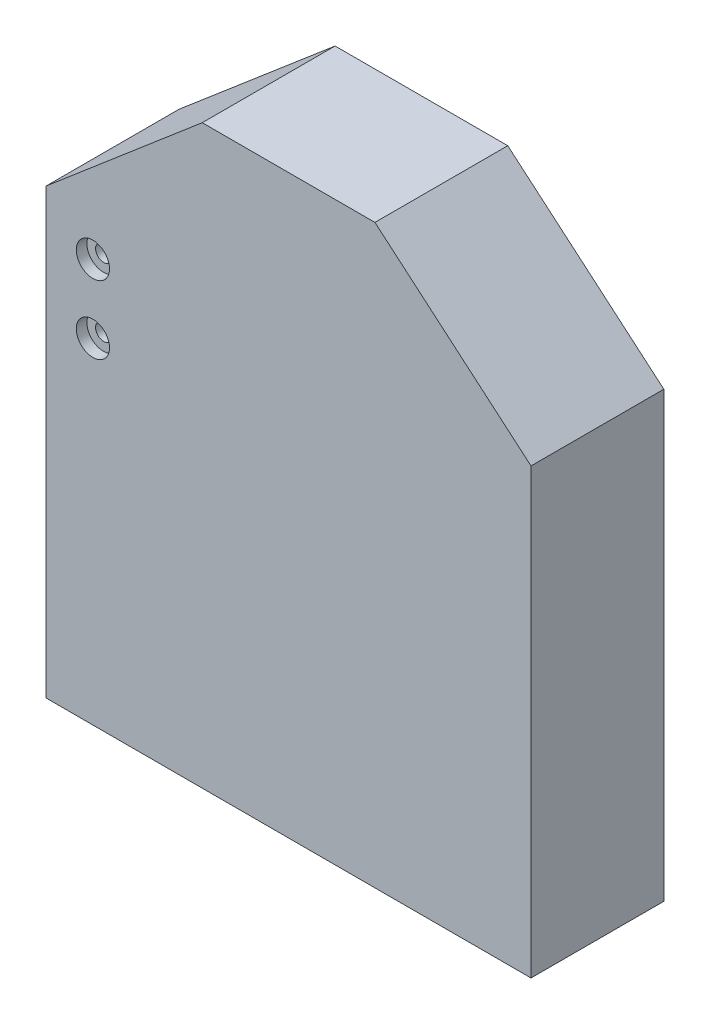
SolidWorks part; units mm, degrees
ref_plane "Front Plane" through (0, 0, 0) normal (0, 0, 1) x (1, 0, 0)
ref_plane "Top Plane" through (0, 0, 0) normal (0, 1, 0) x (1, 0, 0)
ref_plane "Right Plane" through (0, 0, 0) normal (1, 0, 0) x (0, 0, -1)
sketch "Base" plane through (0, 0, 0) normal (0, 0, 1) x (1, 0, 0)
  line L0 (-36.5, 30.8846) -> (-13, 50.8846)
  line L1 (-32.5, -27.5) -> (32.5, -27.5)
  line L2 (-32.5, -27.5) -> (-32.5, 27.5)
  line L3 (-32.5, 27.5) -> (32.5, 27.5)
  line L4 (32.5, -27.5) -> (32.5, 27.5)
  line L5 (-32.5, -27.5) -> (32.5, 27.5) construction
  line L6 (-32.5, 27.5) -> (32.5, -27.5) construction
  line L8 (-36.5, -30.8846) -> (-36.5, 30.8846)
  line L10 (36.5, -30.8846) -> (36.5, 30.8846)
  line L11 (-36.5, -30.8846) -> (36.5, 30.8846) construction
  line L12 (-36.5, 30.8846) -> (36.5, -30.8846) construction
  line L20 (13, 50.8846) -> (36.5, 30.8846)
  line L21 (-36.5, -30.8846) -> (36.5, -30.8846)
  line L22 (-21, -27.5) -> (-21, 5.6)
  line L23 (-21, 5.6) -> (-11, 5.6)
  line L24 (-11, 5.6) -> (-11, -27.5)
  line L25 (-11, -27.5) -> (-21, -27.5)
  line L26 (11, -27.5) -> (11, 5.6)
  line L27 (11, 5.6) -> (21, 5.6)
  line L28 (21, 5.6) -> (21, -27.5)
  line L29 (21, -27.5) -> (11, -27.5)
  line L30 (-21, 3.6) -> (-29, 3.6)
  line L31 (-29, 3.6) -> (-29, -0.4)
  line L32 (-29, -0.4) -> (-21, -0.4)
  line L33 (-21, -0.4) -> (-21, 3.6)
  line L34 (21, 3.6) -> (29, 3.6)
  line L35 (29, 3.6) -> (29, -0.4)
  line L36 (29, -0.4) -> (21, -0.4)
  line L37 (-13, 50.8846) -> (13, 50.8846)
  line L39 (-32.5, 17.1) -> (-18.3, 17.1)
  line L40 (-18.3, 17.1) -> (-18.3, 32.5)
  line L41 (-18.3, 32.5) -> (-32.5, 32.5)
  line L42 (-32.5, 32.5) -> (-32.5, 17.1)
  line L44 (32.5, 17.1) -> (18.3, 17.1)
  line L45 (18.3, 17.1) -> (18.3, 32.5)
  line L46 (18.3, 32.5) -> (32.5, 32.5)
  line L47 (32.5, 32.5) -> (32.5, 17.1)
  line L49 (0, 0) -> (0, 33.5) construction
  line L51 (-9, -27.5) -> (-9, 7.6)
  line L52 (-9, 7.6) -> (-23, 7.6)
  line L54 (-23, 7.6) -> (-23, 3.6)
  line L56 (-23, -0.4) -> (-23, -27.5)
  line L58 (9, -27.5) -> (9, 7.6)
  line L59 (9, 7.6) -> (23, 7.6)
  line L60 (23, 7.6) -> (23, 3.6)
  line L61 (23, -27.5) -> (23, -0.4)
  line L62 (-23, 3.6) -> (-29, 3.6)
  line L63 (-29, -0.4) -> (-23, -0.4)
  line L64 (23, 3.6) -> (29, 3.6)
  line L65 (29, -0.4) -> (23, -0.4)
  line L66 (-22.3, 32.5) -> (-22.3, 17.1)
  line L67 (-26.5, 32.5) -> (-26.5, 27.5)
  line L68 (-26.5, 27.5) -> (-32.5, 27.5)
  line L69 (-26.5, 17.1) -> (-26.5, 22.1)
  line L70 (-26.5, 22.1) -> (-32.5, 22.1)
  line L71 (22.3, 32.5) -> (22.3, 17.1)
  line L72 (26.5, 32.5) -> (26.5, 27.5)
  line L73 (32.5, 22.1) -> (26.5, 22.1)
  line L74 (26.5, 22.1) -> (26.5, 17.1)
  line L75 (-8.4615, 33.5) -> (8.4615, 33.5)
  line L76 (-5.9832, 39.4832) -> (5.9832, 27.5168)
  line L77 (0, 25.0385) -> (0, 41.9615)
  line L78 (-5.9832, 27.5168) -> (5.9832, 39.4832)
  circle A0 centre (0, 33.5) radius 12.5
  circle A1 centre (0, 33.5) radius 8.4615
  point P0 (0, 0)
  point P6 (0, 0)
  point P67 (0, 50.8846)
  point P69 (0, 0)
  point P73 (0, 33.5)
  point P75 (0, 33.5)
  point P78 (0, 33.5)
  point P81 (0, 33.5)
  dimension "D30" = 4
  dimension "D31" = 6
  dimension "D24" = 25
  dimension "D25" = 16.9231
  dimension "D1" = 65
  dimension "D2" = 55
  dimension "D3" = 4
  dimension "D4" = 4
  dimension "D5" = 5
  dimension "D6" = 15.4
  dimension "D7" = 14.2
  dimension "D8" = 33.1
  dimension "D9" = 10
  dimension "D10" = 33.1
  dimension "D11" = 10
  dimension "D12" = 4
  dimension "D13" = 2
  dimension "D14" = 8
  dimension "D15" = 2
  dimension "D16" = 4
  dimension "D17" = 8
  dimension "D18" = 11
  dimension "D19" = 11
  dimension "D20" = 14.2
  dimension "D21" = 15.4
  dimension "D22" = 5
  dimension "D23" = 33.5
  dimension "D26" = 4
  dimension "D27" = 6
  dimension "D28" = 5
  dimension "D29" = 5
  dimension "D32" = 5
  dimension "D33" = 6
  dimension "D34" = 2
  dimension "D35" = 2
  dimension "D36" = 2
  dimension "D37" = 2
  dimension "D38" = 2
  dimension "D39" = 2
  dimension "D40" = 26
  dimension "D41" = 20
  dimension "D42" = 45
  dimension "D43" = 45
ref_plane "Plane1" through (0, 0, 2.2083) normal (0, 0, 1) x (1, 0, 0)
ref_plane "Plane6" through (0, 0, -2) normal (0, 0, 1) x (1, 0, 0)
sketch "Sketch3" plane through (0, 0, 2.2083) normal (0, 0, 1) x (1, 0, 0)
  circle A0 centre (0, 33.5) radius 8.4615
  dimension "D1" = 16.9231
ref_plane "Plane2" through (0, 0, 12) normal (0, 0, 1) x (1, 0, 0)
sketch "Sketch4" plane through (0, 0, 12) normal (0, 0, 1) x (1, 0, 0)
  circle A0 centre (0, 33.5) radius 12.5
  dimension "D1" = 25
ref_plane "Plane3" through (0, 0, 8.7404) normal (0, 0, 1) x (1, 0, 0)
sketch "Sketch5" plane through (0, 0, 8.7404) normal (0, 0, 1) x (1, 0, 0)
  circle A0 centre (0, 33.5) radius 12.5
  dimension "D1" = 25
ref_plane "Plane4" through (0, 0, 0) normal (1, 0, 0) x (0, 1, 0)
sketch "Toilet" plane through (0, 0, 0) normal (1, 0, 0) x (0, 1, 0)
  line L0 (33.5, 12) -> (33.5, 0)
  line L1 (46, 12) -> (21, 12) construction
  line L2 (46, 0) -> (21, 0) construction
  line L3 (21, 8.7404) -> (21, 12)
  line L4 (40.15, 8.7404) -> (-40.15, 8.7404) construction
  line L5 (46, 8.7404) -> (21, 8.7404) construction
  line L6 (40.15, 12) -> (-40.15, 12) construction
  line L7 (21, 12) -> (46, 12)
  line L8 (41.9615, 2.2083) -> (25.0385, 2.2083) construction
  line L9 (40.15, 2.2083) -> (-40.15, 2.2083) construction
  line L10 (25.0385, 2.2083) -> (25.0385, 0)
  line L11 (32.5, 0) -> (17.1, 0) construction
  line L12 (25.0385, 0) -> (41.9615, 0)
  line L13 (41.9615, 2.2083) -> (41.9615, 0)
  line L14 (46, 8.7404) -> (46, 12)
  line L17 (-4.9, 12) -> (-4.9, 0)
  line L18 (4.0615, 2.2083) -> (4.0615, 0)
  line L19 (7.6, 8.7404) -> (7.6, 12)
  line L20 (-4.9, 12) -> (7.6, 12)
  line L21 (4.0615, 0) -> (-4.9, 0)
  line L22 (7.6, 12) -> (21, 12)
  line L23 (7.6, 8.7404) -> (21, 8.7404)
  line L24 (4.0615, 0) -> (25.0385, 0)
  line L25 (7.6, 8.7404) -> (-4.9, 8.7404)
  line L26 (-4.9, 8.7404) -> (-4.9, 0)
  line L27 (7.6, 8.7404) -> (7.6, 0)
  line L28 (7.6, 0) -> (4.0615, 0)
  arc A0 (21, 8.7404) -> (25.0385, 2.2083) centre (18.9289, 2.9455) cw
  arc A1 (46, 8.7404) -> (41.9615, 2.2083) centre (48.0711, 2.9455) ccw
  arc A2 (7.6, 8.7404) -> (4.0615, 2.2083) centre (10.1449, 3.1374) ccw
  point P36 (4.0615, 1.1042)
  dimension "D1" = 6.1538
  dimension "D5" = 6.1538
  dimension "D2" = 8.4615
  dimension "D3" = 12.5
  dimension "D4" = 3.2596
  dimension "D6" = 2.2083
  dimension "D7" = 25.9
  dimension "D8" = 12
  dimension "D9" = 12.5
  dimension "D11" = 3.5385
extrude "Boss-Extrude5" add sketch "Base" against normal blind 2 contours L37 L0 L8 L21 L10 L20 A0 L3 L45 L46 L47 L4 L1 L2 L42 L41 L40 | A1 L3 A0 | L76 A1 L75 | L77 A1 L76 | L78 A1 L77 | L75 A1 L78 | L76 A1 L75 | L3 A1 L76 L77 | L78 A1 L3 L77 | L75 A1 L78 | L3 A1 L77 | L77 A1 L3 | A1 L3 A0 | A0 L3 L40 L39 L2 L1 L56 L32 L31 L30 L54 L52 L51 L58 L59 L60 L34 L35 L36 L61 L4 L44 L45 | L70 L69 L39 L66 L3 L42 | L3 L66 L39 L40 | L41 L66 L3 L40 | L41 L67 L3 L66 | L67 L41 L42 L3 | L69 L70 L2 L39 | L71 L46 L45 L3 | L71 L3 L45 L44 | L74 L73 L47 L3 L71 L44 | L72 L46 L71 L3 | L46 L72 L3 L47 | L73 L74 L44 L4 | L28 L27 L26 L1 | L36 L35 L34 L28 | L1 L61 L36 L28 | L60 L59 L58 L1 L26 L27 L28 L34 | L52 L54 L30 L22 L23 L24 L1 L51 | L24 L23 L22 L1 | L31 L32 L22 L30 | L32 L56 L1 L22 region at (-24.0396, 40.0499, 0) region at (0, 0.2781, 0) region at (-22, -13.95, 0) region at (-29.5, 19.6, 0) region at (-16, -10.95, 0) region at (-25, 1.6, 0) region at (-26.5719, 23.3647, 0) region at (-10.6221, -10.95, 0) region at (-29.5, 30, 0) region at (-20.3, 22.3, 0) region at (-24.4, 30, 0) region at (-20.3, 30, 0) region at (9.3779, -9.95, 0) region at (16, -10.95, 0) region at (-3.0195, 45.3091, 0) region at (0, 24.4153, 0) region at (22, -13.95, 0) region at (-1.9999, 29.5, 0) region at (-2.2882, 26.502, 0) region at (25, 1.6, 0) region at (1.9999, 29.5, 0) region at (2.2882, 26.502, 0) region at (-5.0787, 31.3963, 0) region at (20.3, 30, 0) region at (20.3, 22.3, 0) region at (5.0787, 35.6037, 0) region at (-5.0787, 35.6037, 0) region at (5.0787, 31.3963, 0) region at (-2.1037, 38.5787, 0) region at (2.1037, 38.5787, 0) region at (24.4, 30, 0) region at (26.5719, 23.3647, 0) region at (29.5, 19.6, 0) region at (29.5, 30, 0)
sketch "Sketch7" plane through (0, 0, 12) normal (0, 0, 1) x (1, 0, 0)
  line L0 (-9, 7.6) -> (-9, -30.8846)
  line L1 (-36.5, -30.8846) -> (36.5, -30.8846) construction
  line L2 (-9, -30.8846) -> (9, -30.8846)
  line L3 (9, -30.8846) -> (9, 7.6)
  line L4 (-9, 7.6) -> (-23, 7.6) construction
  line L5 (9, 7.6) -> (23, 7.6) construction
  line L6 (-6, 7.6) -> (-6, -27.5)
  line L7 (-32.5, -27.5) -> (32.5, -27.5) construction
  line L8 (-6, -27.5) -> (6, -27.5)
  line L9 (6, -27.5) -> (6, 7.6)
  line L10 (12.5, 33.5) -> (-12.5, 33.5)
  line L11 (-9, 7.6) -> (9, 7.6)
  line L12 (0, -18.425) -> (0, 18.425) construction
  arc A1 (-16.5, 33.5) -> (-11.5, 20.6) centre (2.641, 33.5) ccw
  arc A2 (-11.5, 20.6) -> (-6, 7.6) centre (-24.1136, 7.6) cw
  arc A3 (16.5, 33.5) -> (11.5, 20.6) centre (-2.641, 33.5) cw
  arc A4 (11.5, 20.6) -> (6, 7.6) centre (24.1136, 7.6) ccw
  circle A6 centre (0, 33.5) radius 12.5 construction
  arc A10 (-16.5, 33.5) -> (-12.5, 19.3) centre (10.705, 33.5) ccw
  arc A11 (-9, 7.6) -> (-12.5, 19.3) centre (-30.3057, 7.6) ccw
  arc A12 (16.5, 33.5) -> (12.5, 19.3) centre (-10.705, 33.5) cw
  arc A13 (9, 7.6) -> (12.5, 19.3) centre (30.3057, 7.6) cw
  ellipse E0 centre (0, 33.5) end of major axis (-16.5, 33.5) minor radius 14.5
  point P48 (0, 33.5)
  point P49 (0, 33.5)
  dimension "D1" = 14.5
  dimension "D11" = 3.5
  dimension "D2" = 2.5
  dimension "D3" = 2.5
  dimension "D4" = 13
  dimension "D5" = 13
  dimension "D6" = 16.5
  dimension "D7" = 3
  dimension "D8" = 3
  dimension "D9" = 0
  dimension "D10" = 0
  dimension "D12" = 11.7
extrude "Boss-Extrude6" add sketch "Sketch1<9>" along normal blind 12 contours A0 L3 L40 L39 L2 L1 L56 L32 L31 L30 L54 L52 L51 L58 L59 L60 L34 L35 L36 L61 L4 L44 L45 | L52 L54 L30 L22 L23 L24 L1 L51 | L32 L56 L1 L22 | L60 L59 L58 L1 L26 L27 L28 L34 | L1 L61 L36 L28 | L37 L0 L8 L21 L10 L20 A0 L3 L45 L46 L47 L4 L1 L2 L42 L41 L40 | A1 L3 A0 | A1 L3 A0 | L76 A1 L75 | L75 A1 L78 | L78 A1 L77 | L77 A1 L76 | L76 A1 L75 | L75 A1 L78 | L78 A1 L3 L77 | L3 A1 L76 L77 | L77 A1 L3 | L3 A1 L77 region at (-24.0396, 40.0499, 0) region at (0, 0.2781, 0) region at (-22, -13.95, 0) region at (-10.6221, -10.95, 0) region at (9.3779, -9.95, 0) region at (-3.0195, 45.3091, 0) region at (0, 24.4153, 0) region at (22, -13.95, 0) region at (-1.9999, 29.5, 0) region at (-2.2882, 26.502, 0) region at (1.9999, 29.5, 0) region at (2.2882, 26.502, 0) region at (-5.0787, 31.3963, 0) region at (5.0787, 35.6037, 0) region at (-5.0787, 35.6037, 0) region at (5.0787, 31.3963, 0) region at (-2.1037, 38.5787, 0) region at (2.1037, 38.5787, 0)
sketch "Sketch1<9>" plane through (0, 0, 0) normal (0, 0, 1) x (1, 0, 0) same geometry as "Base"
revolve "Cut-Revolve2" cut sketch "Toilet" angle 360 about L0 region at (0, 38.6826, 6.5515)
extrude "Cut-Extrude3" cut sketch "Sketch3" against normal blind 12
extrude "Cut-Extrude9" cut sketch "Sketch7" against normal blind 3.2596 contours E0 L6 L8 L9 | E0 L10 region at (0, -9.95, 12) region at (0, 47.5607, 12)
extrude "Cut-Extrude10" cut sketch "Sketch7<6>" against normal blind 12 contours L6 L8 L9 region at (0, -9.95, 12)
sketch "Sketch7<6>" plane through (0, 0, 12) normal (0, 0, 1) x (1, 0, 0) same geometry as "Sketch7"
extrude "Cut-Extrude11" cut sketch "Sketch7<7>" against normal blind 3.2596 contours E0 | E0 A1 A2 L11 A4 A3 region at (0, 15.5003, 12) region at (0, 47.5607, 12)
sketch "Sketch7<7>" plane through (0, 0, 12) normal (0, 0, 1) x (1, 0, 0) same geometry as "Sketch7"
extrude "Boss-Extrude7" add sketch "Sketch7<5>" against normal blind 12 contours E0 A1 L0 L2 L3 A3 L9 L8 L6 region at (-7.5, 7.1751, 12)
sketch "Sketch7<5>" plane through (0, 0, 12) normal (0, 0, 1) x (1, 0, 0) same geometry as "Sketch7"
sketch "Sketch8" plane through (0, 0, 12) normal (0, 0, 1) x (1, 0, 0)
  line L0 (-36.5, 30.8846) -> (-36.5, -30.8846)
  line L1 (-36.5, -30.8846) -> (36.5, -30.8846)
  line L2 (36.5, -30.8846) -> (36.5, 30.8846)
  line L3 (36.5, 30.8846) -> (13, 50.8846)
  line L4 (13, 50.8846) -> (-13, 50.8846)
  line L5 (-13, 50.8846) -> (-36.5, 30.8846)
extrude "Boss-Extrude8" add sketch "Sketch8" along normal blind 6
sketch "Sketch9" plane through (0, 0, 12) normal (0, 0, 1) x (1, 0, 0)
  line L0 (-23, 7.6) -> (-23, 13.6)
  line L1 (-23, 13.6) -> (-29, 13.6)
  line L2 (-29, 13.6) -> (-29, 3.6)
  line L3 (-29, -0.4) -> (-29, -10.4)
  line L4 (-29, -10.4) -> (-23, -10.4)
  line L5 (-23, -0.4) -> (-23, -27.5) construction
  line L6 (-23, -10.4) -> (-23, -0.4)
  line L7 (-29, -0.4) -> (-21, -0.4) construction
  line L8 (-21, 3.6) -> (-29, 3.6) construction
  line L9 (-23, 7.6) -> (-23, 3.6)
  line L10 (-23, 3.6) -> (-29, 3.6)
  line L11 (-29, -0.4) -> (-23, -0.4)
  line L12 (0, -18.425) -> (0, 18.425) construction
  line L13 (29, -0.4) -> (23, -0.4)
  line L14 (23, 3.6) -> (29, 3.6)
  line L15 (23, 7.6) -> (23, 3.6)
  line L16 (23, -10.4) -> (23, -0.4)
  line L17 (29, -10.4) -> (23, -10.4)
  line L18 (29, -0.4) -> (29, -10.4)
  line L19 (29, 13.6) -> (29, 3.6)
  line L20 (23, 13.6) -> (29, 13.6)
  line L21 (23, 7.6) -> (23, 13.6)
  line L22 (-29, 3.6) -> (-29, -0.4)
  line L23 (-23, 3.6) -> (-23, -0.4)
  line L24 (23, 3.6) -> (23, -0.4)
  line L25 (29, 3.6) -> (29, -0.4)
  dimension "D1" = 10
  dimension "D2" = 10
extrude "Cut-Extrude14" cut sketch "Sketch9" against normal up to next contours L23 L10 L22 L11 | L10 L9 L0 L1 L2 | L11 L3 L4 L6 | L21 L15 L14 L19 L20 | L25 L14 L24 L13 | L18 L13 L16 L17 region at (-26, 8.6, 12) region at (-26, 1.6, 12) region at (-26, -5.4, 12) region at (26, -5.4, 12) region at (26, 1.6, 12) region at (26, 8.6, 12)
extrude "Boss-Extrude11" add sketch "Sketch6<10>" along normal blind 6 and the other way blind 6 contours L27 A2 L18 L24 | A2 L25 L17 L21 L18 region at (0, 5.9872, 3.714) region at (0, -0.0753, 4.5719)
sketch "Sketch6<10>" plane through (0, 0, 0) normal (1, 0, 0) x (0, 1, 0) same geometry as "Toilet"
extrude "Cut-Extrude15" cut sketch "Sketch6<11>" against normal blind 6 and the other way blind 6 contours A2 L25 L17 L21 L18 region at (0, -0.0753, 4.5719)
sketch "Sketch6<11>" plane through (0, 0, 0) normal (1, 0, 0) x (0, 1, 0) same geometry as "Toilet"
extrude "Cut-Extrude16" cut sketch "Sketch1<10>" against normal blind 6 contours L70 L69 L39 L66 L3 L42 | L41 L67 L3 L66 | L74 L73 L47 L3 L71 L44 | L72 L46 L71 L3 region at (-26.5719, 23.3647, 0) region at (-24.4, 30, 0) region at (24.4, 30, 0) region at (26.5719, 23.3647, 0)
sketch "Sketch1<10>" plane through (0, 0, 0) normal (0, 0, 1) x (1, 0, 0) same geometry as "Base"
sketch "Sketch13" plane through (0, 0, 12) normal (0, 0, 1) x (1, 0, 0)
  line L3 (36.5, 30.8846) -> (36.5, 35.8846)
  line L4 (36.5, 35.8846) -> (13, 55.8846)
  line L5 (13, 55.8846) -> (-13, 55.8846)
  line L6 (-13, 55.8846) -> (-36.5, 35.8846)
  line L7 (-36.5, 35.8846) -> (-36.5, 30.8846)
  line L8 (-36.5, 30.8846) -> (-13, 50.8846)
  line L9 (-13, 50.8846) -> (13, 50.8846)
  line L10 (13, 50.8846) -> (36.5, 30.8846)
  dimension "D1" = 5
extrude "Boss-Extrude12" add sketch "Sketch13" against normal blind 14 and the other way blind 6
ref_plane "Plane7" through (0, 0, 0) normal (0, 0, 1) x (1, 0, 0)
hole_wizard "CBORE for M2 Pan Head Screw1" positions "Sketch16" profile "Sketch17" counterbore size "M2" standard "ISO"
sketch "Sketch16" plane through (0, 0, 18) normal (0, 0, 1) x (1, 0, 0)
  point P0 (-29.4609, 19.5418)
  point P2 (-29.4609, 29.8387)
sketch "Sketch17" plane through (-29.4609, 19.5418, 18) normal (1, 0, 0) x (0, -1, 0)
  line L0 (0, 0) -> (0, 18.321)
  line L1 (0, 18.321) -> (1.2, 17.6)
  line L2 (1.2, 17.6) -> (1.2, 1.6)
  line L3 (1.2, 1.6) -> (2.5, 1.6)
  line L4 (2.5, 1.6) -> (2.5, 0)
  line L5 (2.5, 0) -> (0, 0)
  line L10 (0, 18.321) -> (-1.2, 17.6) construction
  line L11 (0, -6.35) -> (0, 107.95) construction
  dimension "Hole Dia." = 2.4
  dimension "Hole Depth" = 17.6
  dimension "C'Bore Dia." = 5
  dimension "C'Bore Depth" = 1.6
  dimension "Drill Angle" = 118
sketch "Sketch18" plane through (0, 0, 0) normal (1, 0, 0) x (0, 1, 0)
  line L0 (-27.5, 0) -> (1.6, 0)
  line L2 (-30.8846, 0) -> (30.8846, 0) construction
  line L3 (1.6, 0) -> (1.6, 6)
  line L4 (-30.8846, 0) -> (30.8846, 0) construction
  circle A0 centre (1.6, 6) radius 9.5
  dimension "D3" = 19
  dimension "D1" = 29.1
  dimension "D2" = 6
